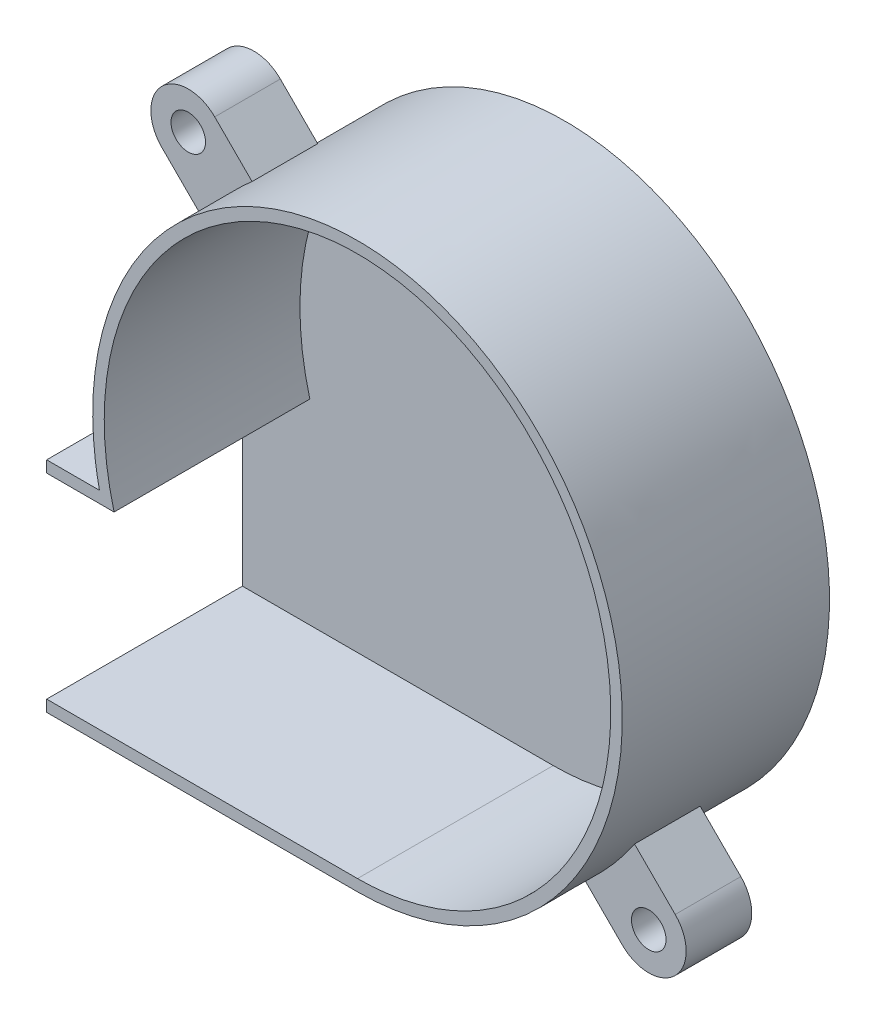
SolidWorks part; units mm, degrees
ref_plane "Plano frontal" through (0, 0, 0) normal (0, 0, 1) x (1, 0, 0)
ref_plane "Plano superior" through (0, 0, 0) normal (0, 1, 0) x (1, 0, 0)
ref_plane "Plano direito" through (0, 0, 0) normal (1, 0, 0) x (0, 0, -1)
sketch "Esboço1" plane through (0, 0, 0) normal (0, 0, 1) x (1, 0, 0)
  line L0 (0, -24.5) -> (-27, -24.5)
  line L1 (-27, -24.5) -> (-27, -5.5)
  line L2 (-27, -5.5) -> (-22.413, -5.5)
  line L3 (0, -23.5) -> (-26, -23.5)
  line L4 (-26, -23.5) -> (-26, -6.5)
  line L5 (-26, -6.5) -> (-21.1416, -6.5)
  line L6 (-26, -6.5) -> (-27, -6.5)
  line L8 (-27, -23.5) -> (-26, -23.5)
  ellipse E0 centre (0, 0) end of major axis (0, 24.5) minor radius 23 (0, -24.5) -> (-22.413, -5.5) ccw
  spline S0 degree 1 poles (0, -23.5) (-21.1416, -6.5) knots 0 0 1 1 construction
  spline S1 degree 3 poles (-21.1416, -6.5) (-21.7759, -4.1462) (-22.35, 0.7769) (-21.0411, 8.0855) (-17.6937, 14.6033) (-12.642, 19.6989) (-6.3826, 22.8884) (0.482, 23.8764) (7.3009, 22.5731) (13.4272, 19.0971) (18.2691, 13.7715) (21.3496, 7.1038) (22.3606, -0.259) (21.2003, -7.5965) (17.9858, -14.1907) (13.037, -19.4026) (6.8455, -22.7361) (2.2763, -23.5) (0, -23.5) knots -3.141593 -3.141593 -3.141593 -3.141593 -2.829596 -2.5176 -2.205603 -1.893607 -1.58161 -1.269614 -0.957618 -0.645621 -0.333625 -0.021628 0.290368 0.602365 0.914361 1.226357 1.538354 1.85035 1.85035 1.85035 1.85035
  dimension "D1" = 49
  dimension "D5" = 1
  dimension "D2" = 46
  dimension "D3" = 50
  dimension "D4" = 19
extrude "Ressalto-extrusão1" add sketch "Esboço1" along normal blind 1 contours E0 L2 L1 L0
extrude "Ressalto-extrusão2" add sketch "Esboço1<3>" along normal blind 18 contours L5 S1 L3 L8 L1 L0 E0 L2 L6 region at (-13.5, -23.7999, 0)
sketch "Esboço1<3>" plane through (0, 0, 0) normal (0, 0, 1) x (1, 0, 0) same geometry as "Esboço1"
sketch "Esboço2" plane through (0, 0, 0) normal (0, 0, 1) x (1, 0, 0)
  line L0 (-20, 20) -> (20, -20) construction
  line L1 (-27, -23.5) -> (0, -23.5) construction
  line L2 (22.2981, -17.7019) -> (18.7642, -14.168)
  line L3 (-14.458, 19.0542) -> (-17.7019, 22.2981)
  line L4 (17.7019, -22.2981) -> (14.458, -19.0542)
  line L5 (-18.7642, 14.168) -> (-22.2981, 17.7019)
  arc A0 (-17.7019, 22.2981) -> (-22.2981, 17.7019) centre (-20, 20) ccw
  arc A1 (17.7019, -22.2981) -> (22.2981, -17.7019) centre (20, -20) ccw
  circle A2 centre (20, -20) radius 1.5
  circle A3 centre (-20, 20) radius 1.5
  ellipse E0 centre (0, 0) end of major axis (0, 24.5) minor radius 23 (0, -24.5) -> (-22.413, -5.5) ccw construction
  ellipse E1 centre (0, 0) end of major axis (0, 24.5) minor radius 23 (14.458, -19.0542) -> (18.7642, -14.168) ccw
  ellipse E2 centre (0, 0) end of major axis (0, 24.5) minor radius 23 (-14.458, 19.0542) -> (-18.7642, 14.168) ccw
  point P6 (0, 0)
  dimension "D3" = 3
  dimension "D4" = 6.5
  dimension "D1" = 40
  dimension "D2" = 45
extrude "Ressalto-extrusão3" add sketch "Esboço2" along normal blind 5.7 from offset 7
